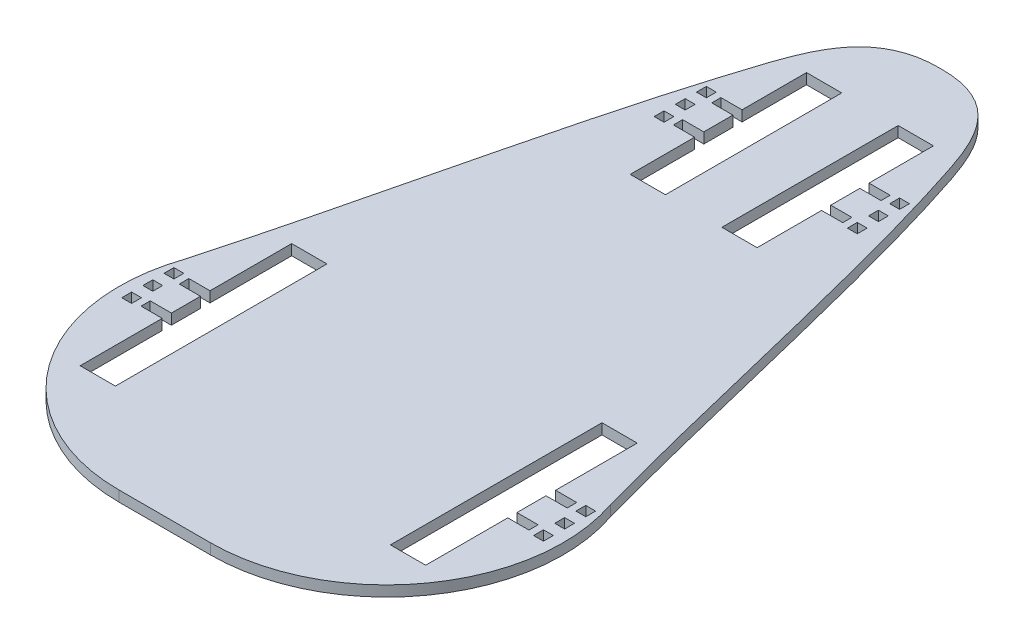
SolidWorks part; units mm, degrees
ref_plane "Front Plane" through (0, 0, 0) normal (0, 0, 1) x (1, 0, 0)
ref_plane "Top Plane" through (0, 0, 0) normal (0, 1, 0) x (1, 0, 0)
ref_plane "Right Plane" through (0, 0, 0) normal (1, 0, 0) x (0, 0, -1)
sketch "Sketch1" plane through (0, 0, 0) normal (0, 1, 0) x (1, 0, 0)
  line L0 (54.9211, 210.7172) -> (54.9211, -9.2828) construction
  line L1 (41.947, -9.2828) -> (67.8952, -9.2828)
  line L6 (5.9211, 75.7172) -> (15.9211, 75.7172)
  line L7 (54.9211, -9.2828) -> (64.9211, -9.2828)
  line L8 (54.9211, -9.2828) -> (44.9211, -9.2828)
  line L9 (5.9211, 75.7172) -> (5.9211, 15.7172)
  line L10 (5.9211, 15.7172) -> (15.9211, 15.7172)
  line L11 (15.9211, 75.7172) -> (15.9211, 15.7172)
  line L12 (5.9211, 75.7172) -> (15.9211, 15.7172) construction
  line L13 (5.9211, 15.7172) -> (15.9211, 75.7172) construction
  line L18 (-0.0789, 52.5482) -> (5.9211, 52.5482)
  line L19 (-0.0789, 52.5482) -> (-0.0789, 49.8422)
  line L35 (103.9211, 15.7172) -> (93.9211, 15.7172)
  line L36 (93.9211, 75.7172) -> (93.9211, 15.7172)
  line L37 (103.9211, 75.7172) -> (93.9211, 75.7172)
  line L38 (103.9211, 75.7172) -> (103.9211, 15.7172)
  line L40 (36.9211, 190.7172) -> (46.9211, 190.7172)
  line L41 (36.9211, 190.7172) -> (36.9211, 140.7172)
  line L42 (36.9211, 140.7172) -> (46.9211, 140.7172)
  line L43 (46.9211, 190.7172) -> (46.9211, 140.7172)
  line L44 (36.9211, 190.7172) -> (46.9211, 140.7172) construction
  line L45 (36.9211, 140.7172) -> (46.9211, 190.7172) construction
  line L46 (10.9211, 45.7172) -> (-10.3167, 45.7172) construction
  line L63 (72.9211, 140.7172) -> (62.9211, 140.7172)
  line L64 (62.9211, 190.7172) -> (62.9211, 140.7172)
  line L65 (72.9211, 190.7172) -> (62.9211, 190.7172)
  line L66 (72.9211, 190.7172) -> (72.9211, 140.7172)
  line L78 (114.7211, 47.1172) -> (111.9211, 44.3172) construction
  line L79 (114.7211, 44.3172) -> (111.9211, 47.1172) construction
  line L80 (114.7211, 50.3172) -> (111.9211, 53.1172) construction
  line L81 (114.7211, 53.1172) -> (111.9211, 50.3172) construction
  line L82 (109.9211, 38.9922) -> (103.9211, 41.5922) construction
  line L83 (109.9211, 41.5922) -> (103.9211, 38.9922) construction
  line L84 (109.9211, 49.8422) -> (103.9211, 52.5482) construction
  line L85 (109.9211, 52.5482) -> (103.9211, 49.8422) construction
  line L86 (111.9211, 41.1172) -> (111.9211, 38.3172)
  line L87 (114.7211, 38.3172) -> (111.9211, 38.3172)
  line L88 (114.7211, 41.1172) -> (114.7211, 38.3172)
  line L89 (111.9211, 44.3172) -> (111.9211, 47.1172)
  line L90 (114.7211, 47.1172) -> (111.9211, 47.1172)
  line L91 (114.7211, 44.3172) -> (114.7211, 47.1172)
  line L92 (41.9211, 165.7172) -> (25.0295, 165.7172) construction
  line L93 (30.9211, 172.4422) -> (36.9211, 172.4422)
  line L94 (30.9211, 172.4422) -> (30.9211, 169.8422)
  line L95 (30.9211, 169.8422) -> (36.9211, 169.8422)
  line L96 (36.9211, 172.4422) -> (36.9211, 169.8422)
  line L97 (30.9211, 172.4422) -> (36.9211, 169.8422) construction
  line L98 (30.9211, 169.8422) -> (36.9211, 172.4422) construction
  line L103 (26.1211, 161.1172) -> (28.9211, 161.1172)
  line L104 (26.1211, 173.1172) -> (28.9211, 173.1172)
  line L105 (30.9211, 161.5922) -> (36.9211, 161.5922)
  line L106 (30.9211, 161.5922) -> (30.9211, 158.9922)
  line L107 (30.9211, 158.9922) -> (36.9211, 158.9922)
  line L108 (36.9211, 161.5922) -> (36.9211, 158.9922)
  line L109 (30.9211, 161.5922) -> (36.9211, 158.9922) construction
  line L110 (30.9211, 158.9922) -> (36.9211, 161.5922) construction
  line L111 (26.1211, 173.1172) -> (26.1211, 170.3172)
  line L112 (26.1211, 170.3172) -> (28.9211, 170.3172)
  line L113 (28.9211, 173.1172) -> (28.9211, 170.3172)
  line L114 (26.1211, 173.1172) -> (28.9211, 170.3172) construction
  line L115 (26.1211, 170.3172) -> (28.9211, 173.1172) construction
  line L116 (26.1211, 164.3172) -> (28.9211, 164.3172)
  line L117 (26.1211, 164.3172) -> (26.1211, 167.1172)
  line L118 (26.1211, 167.1172) -> (28.9211, 167.1172)
  line L119 (28.9211, 164.3172) -> (28.9211, 167.1172)
  line L120 (26.1211, 164.3172) -> (28.9211, 167.1172) construction
  line L121 (26.1211, 167.1172) -> (28.9211, 164.3172) construction
  line L122 (26.1211, 161.1172) -> (26.1211, 158.3172)
  line L123 (26.1211, 158.3172) -> (28.9211, 158.3172)
  line L124 (28.9211, 161.1172) -> (28.9211, 158.3172)
  line L125 (83.7211, 167.1172) -> (80.9211, 164.3172) construction
  line L126 (83.7211, 164.3172) -> (80.9211, 167.1172) construction
  line L127 (83.7211, 170.3172) -> (80.9211, 173.1172) construction
  line L128 (83.7211, 173.1172) -> (80.9211, 170.3172) construction
  line L129 (78.9211, 158.9922) -> (72.9211, 161.5922) construction
  line L130 (78.9211, 161.5922) -> (72.9211, 158.9922) construction
  line L131 (78.9211, 169.8422) -> (72.9211, 172.4422) construction
  line L132 (78.9211, 172.4422) -> (72.9211, 169.8422) construction
  line L133 (80.9211, 161.1172) -> (80.9211, 158.3172)
  line L134 (83.7211, 158.3172) -> (80.9211, 158.3172)
  line L135 (83.7211, 161.1172) -> (83.7211, 158.3172)
  line L136 (80.9211, 164.3172) -> (80.9211, 167.1172)
  line L137 (83.7211, 167.1172) -> (80.9211, 167.1172)
  line L138 (83.7211, 164.3172) -> (83.7211, 167.1172)
  line L139 (83.7211, 164.3172) -> (80.9211, 164.3172)
  line L140 (80.9211, 173.1172) -> (80.9211, 170.3172)
  line L141 (83.7211, 170.3172) -> (80.9211, 170.3172)
  line L142 (83.7211, 173.1172) -> (83.7211, 170.3172)
  line L143 (72.9211, 161.5922) -> (72.9211, 158.9922)
  line L144 (78.9211, 158.9922) -> (72.9211, 158.9922)
  line L145 (78.9211, 161.5922) -> (78.9211, 158.9922)
  line L146 (78.9211, 161.5922) -> (72.9211, 161.5922)
  line L147 (83.7211, 173.1172) -> (80.9211, 173.1172)
  line L148 (83.7211, 161.1172) -> (80.9211, 161.1172)
  line L149 (72.9211, 172.4422) -> (72.9211, 169.8422)
  line L150 (78.9211, 169.8422) -> (72.9211, 169.8422)
  line L151 (78.9211, 172.4422) -> (78.9211, 169.8422)
  line L152 (78.9211, 172.4422) -> (72.9211, 172.4422)
  line L153 (-0.0789, 49.8422) -> (5.9211, 49.8422)
  line L154 (5.9211, 52.5482) -> (5.9211, 49.8422)
  line L155 (-0.0789, 52.5482) -> (5.9211, 49.8422) construction
  line L156 (-0.0789, 49.8422) -> (5.9211, 52.5482) construction
  line L157 (-4.8789, 41.1172) -> (-2.0789, 41.1172)
  line L158 (-4.8789, 53.1172) -> (-2.0789, 53.1172)
  line L159 (-0.0789, 41.5922) -> (5.9211, 41.5922)
  line L160 (-0.0789, 41.5922) -> (-0.0789, 38.9922)
  line L161 (-0.0789, 38.9922) -> (5.9211, 38.9922)
  line L162 (5.9211, 41.5922) -> (5.9211, 38.9922)
  line L163 (-0.0789, 41.5922) -> (5.9211, 38.9922) construction
  line L164 (-0.0789, 38.9922) -> (5.9211, 41.5922) construction
  line L165 (-4.8789, 53.1172) -> (-4.8789, 50.3172)
  line L166 (-4.8789, 50.3172) -> (-2.0789, 50.3172)
  line L167 (-2.0789, 53.1172) -> (-2.0789, 50.3172)
  line L168 (-4.8789, 53.1172) -> (-2.0789, 50.3172) construction
  line L169 (-4.8789, 50.3172) -> (-2.0789, 53.1172) construction
  line L170 (-4.8789, 44.3172) -> (-2.0789, 44.3172)
  line L171 (-4.8789, 44.3172) -> (-4.8789, 47.1172)
  line L172 (-4.8789, 47.1172) -> (-2.0789, 47.1172)
  line L173 (-2.0789, 44.3172) -> (-2.0789, 47.1172)
  line L174 (-4.8789, 44.3172) -> (-2.0789, 47.1172) construction
  line L175 (-4.8789, 47.1172) -> (-2.0789, 44.3172) construction
  line L176 (-4.8789, 41.1172) -> (-4.8789, 38.3172)
  line L177 (-4.8789, 38.3172) -> (-2.0789, 38.3172)
  line L178 (-2.0789, 41.1172) -> (-2.0789, 38.3172)
  line L179 (114.7211, 44.3172) -> (111.9211, 44.3172)
  line L180 (111.9211, 53.1172) -> (111.9211, 50.3172)
  line L181 (114.7211, 50.3172) -> (111.9211, 50.3172)
  line L182 (114.7211, 53.1172) -> (114.7211, 50.3172)
  line L183 (103.9211, 41.5922) -> (103.9211, 38.9922)
  line L184 (109.9211, 38.9922) -> (103.9211, 38.9922)
  line L185 (109.9211, 41.5922) -> (109.9211, 38.9922)
  line L186 (109.9211, 41.5922) -> (103.9211, 41.5922)
  line L187 (114.7211, 53.1172) -> (111.9211, 53.1172)
  line L188 (114.7211, 41.1172) -> (111.9211, 41.1172)
  line L189 (103.9211, 52.5482) -> (103.9211, 49.8422)
  line L190 (109.9211, 49.8422) -> (103.9211, 49.8422)
  line L191 (109.9211, 52.5482) -> (109.9211, 49.8422)
  line L192 (109.9211, 52.5482) -> (103.9211, 52.5482)
  line L193 (103.9211, 45.7172) -> (5.9211, 45.7172) construction
  arc A0 (41.947, -9.2828) -> (-5.4028, 56.7793) centre (41.947, 40.7172) cw
  arc A1 (67.8952, -9.2828) -> (115.245, 56.7793) centre (67.8952, 40.7172) ccw
  spline S0 degree 3 poles (54.9211, 210.7172) (54.0308, 210.7172) (36.7248, 210.3077) (26.6736, 181.7821) (12.5146, 130.3071) (2.5819, 85.5886) (-5.4028, 56.7793) knots 0 0 0 0 0.011068 0.221366 0.459883 1 1 1 1
  spline S1 degree 3 poles (54.9211, 210.7172) (55.8114, 210.7172) (73.1174, 210.3077) (83.1686, 181.7821) (97.3276, 130.3071) (107.2603, 85.5886) (115.245, 56.7793) knots 0 0 0 0 0.011068 0.221366 0.459883 1 1 1 1
  point P4 (2.9211, 51.1952)
  point P21 (120, 0)
  point P24 (10.9211, 45.7172)
  point P30 (-3.4789, 51.7172)
  point P33 (2.9211, 40.2922)
  point P40 (-3.4789, 45.7172)
  point P50 (41.9211, 165.7172)
  point P67 (33.9211, 171.1422)
  point P82 (27.5211, 171.7172)
  point P85 (33.9211, 160.2922)
  point P92 (27.5211, 165.7172)
  point P121 (82.3211, 165.7172)
  point P122 (75.9211, 160.2922)
  point P123 (82.3211, 171.7172)
  point P124 (75.9211, 171.1422)
  point P131 (113.3211, 45.7172)
  point P132 (106.9211, 40.2922)
  point P133 (113.3211, 51.7172)
  point P134 (106.9211, 51.1952)
  dimension "D6" = 10
  dimension "D7" = 50
  dimension "D10" = 6
  dimension "D2" = 173.1277
  dimension "D1" = 220
  dimension "D3" = 60.3239
  dimension "D4" = 10
  dimension "D5" = 10
  dimension "D8" = 60
  dimension "D9" = 6
  dimension "D11" = 25
  dimension "D12" = 2.8
  dimension "D13" = 2.8
  dimension "D14" = 2.8
  dimension "D15" = 2.8
  dimension "D16" = 2
  dimension "D17" = 2
  dimension "D18" = 39
  dimension "D19" = 2.8
  dimension "D20" = 10
  dimension "D21" = 50
  dimension "D22" = 20
  dimension "D23" = 8
  dimension "D24" = 8.25
  dimension "D25" = 0
  dimension "D26" = 0
  dimension "D27" = 3.2
  dimension "D28" = 3.2
  dimension "D29" = 8.25
  dimension "D30" = 4.125
  dimension "D33" = 2.8
  dimension "D34" = 6
  dimension "D35" = 2.6
  dimension "D36" = 8.25
  dimension "D37" = 4.125
  dimension "D38" = 2.6
  dimension "D39" = 6
  dimension "D40" = 0
  dimension "D41" = 0
  dimension "D42" = 2.8
  dimension "D43" = 2.8
  dimension "D44" = 2.8
  dimension "D45" = 2.8
  dimension "D46" = 2
  dimension "D47" = 2
  dimension "D48" = 3.2
  dimension "D49" = 2.8
  dimension "D50" = 2.8
  dimension "D51" = 3.2
  dimension "D52" = 2
  dimension "D53" = 52
  dimension "D54" = 2
extrude "Boss-Extrude1" add sketch "Sketch1" along normal blind 3 contours L0 S0 A0 L1 | S1 L0 L1 A1 region at (54.9211, 0, -83.3979)
